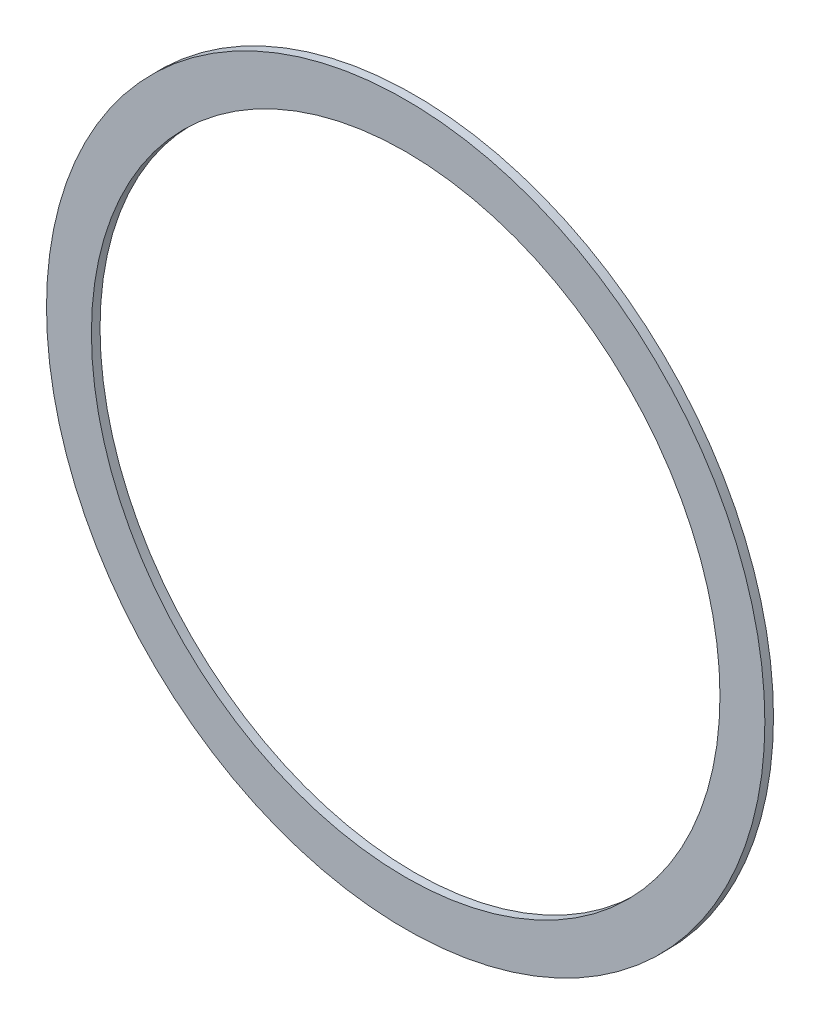
SolidWorks part; units mm, degrees
material "Balsa"
ref_plane "Front Plane" through (0, 0, 0) normal (0, 0, 1) x (1, 0, 0)
ref_plane "Top Plane" through (0, 0, 0) normal (0, 1, 0) x (1, 0, 0)
ref_plane "Right Plane" through (0, 0, 0) normal (1, 0, 0) x (0, 0, -1)
sketch "Sketch2" plane through (0, 0, 0) normal (0, 0, 1) x (1, 0, 0)
  line L0 (0, 0) -> (0, 236.6718) construction
  line L1 (-1.651, 128.5137) -> (-1.651, 121.4017) construction
  line L3 (1.651, 128.5137) -> (1.651, 121.4017) construction
  line L4 (-1.651, 121.4017) -> (1.651, 121.4017) construction
  line L5 (-136.2076, -77.8947) -> (0.0002, 0.7357) construction
  line L6 (-136.2076, -77.8947) -> (0.0002, 0.7357) construction
  line L7 (136.2041, -77.9016) -> (0.0002, 0.7357) construction
  line L8 (136.2041, -77.9016) -> (0.0002, 0.7357) construction
  line L9 (-116.9771, -64.8869) -> (-110.0184, -60.8698) construction
  line L10 (-115.4068, -67.7931) -> (-108.3675, -63.7295) construction
  line L11 (-110.0184, -60.8698) -> (-108.3675, -63.7295) construction
  line L12 (-117.5533, -65.2196) -> (-116.9771, -64.8869) construction
  line L13 (-115.9024, -68.0792) -> (-115.4068, -67.7931) construction
  line L14 (115.4068, -67.7931) -> (109.2475, -64.2371) construction
  line L15 (110.8985, -61.3775) -> (109.2475, -64.2371) construction
  line L16 (116.9771, -64.8869) -> (110.8985, -61.3775) construction
  arc A0 (-1.651, 128.5137) -> (-116.9771, -64.8869) centre (0, -3.556) ccw
  arc A1 (0.0665, 128.1531) -> (63.0696, -118.8475) centre (0, -3.3993) ccw construction
  circle A2 centre (0, -3.556) radius 115.57
  arc A3 (63.0696, -118.8475) -> (0.0665, 128.1531) centre (0, -3.3993) ccw construction
  arc A4 (0, 128.524) -> (-1.651, 128.5137) centre (0, -3.556) ccw
  circle A5 centre (0, -3.556) radius 132.08 construction
  arc A6 (1.651, 128.5137) -> (0, 128.524) centre (0, -3.556) ccw
  arc A7 (-116.9771, -64.8869) -> (-116.2009, -66.3452) centre (0, -3.556) ccw
  arc A8 (-115.4068, -67.7931) -> (115.4068, -67.7931) centre (0, -3.556) ccw
  arc A9 (-116.2009, -66.3452) -> (-115.4068, -67.7931) centre (0, -3.556) ccw
  arc A10 (115.4068, -67.7931) -> (116.1978, -66.3509) centre (0, -3.556) ccw
  arc A11 (116.9771, -64.8869) -> (1.651, 128.5137) centre (0, -3.556) ccw
  arc A12 (116.1978, -66.3509) -> (116.9771, -64.8869) centre (0, -3.556) ccw
  point P24 (-115.4068, -67.7931)
  dimension "D1" = 3.556
  dimension "D3" = 264.16
  dimension "D2" = 16.51
  dimension "D4" = 3.302
  dimension "D5" = 7.112
  dimension "D6" = 3.302
  dimension "D7" = 8.128
  dimension "D8" = 7.076
extrude "Boss-Extrude1" add sketch "Sketch2" along normal mid plane 3.175
